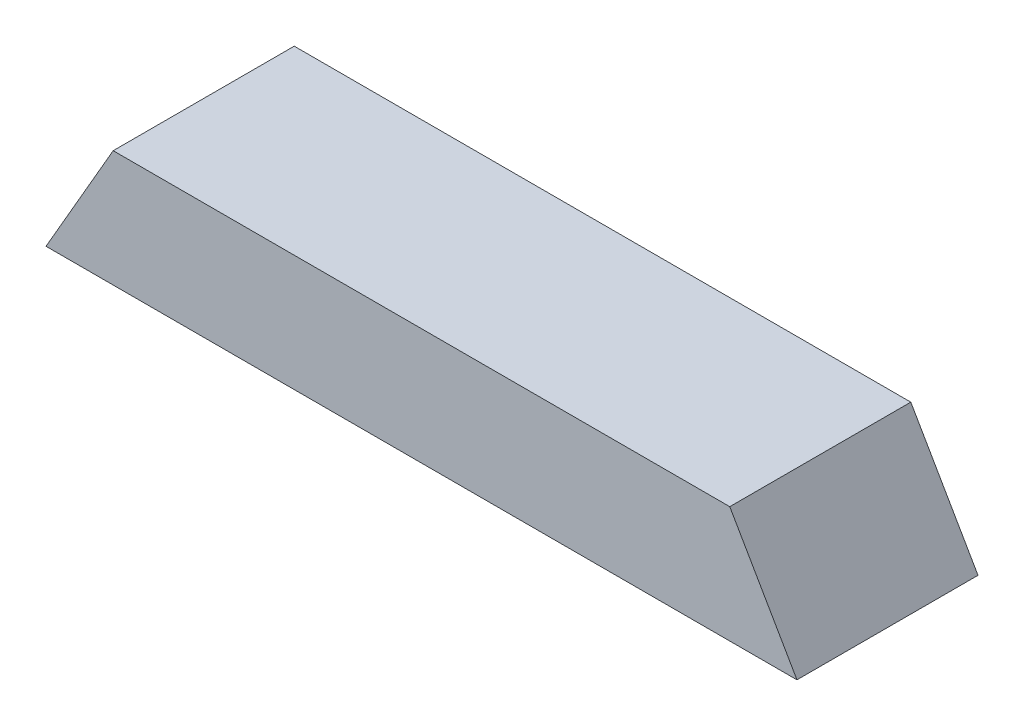
SolidWorks part; units mm, degrees
ref_plane "Front Plane" through (0, 0, 0) normal (0, 0, 1) x (1, 0, 0)
ref_plane "Top Plane" through (0, 0, 0) normal (0, 1, 0) x (1, 0, 0)
ref_plane "Right Plane" through (0, 0, 0) normal (1, 0, 0) x (0, 0, -1)
sketch "Sketch1" plane through (0, 0, 0) normal (0, 1, 0) x (1, 0, 0)
  line L1 (0, 0) -> (26, 0)
  line L2 (0, 0) -> (0, 5.6)
  line L3 (0, 5.6) -> (26, 5.6)
  line L4 (26, 0) -> (26, 5.6)
  dimension "D1" = 26
  dimension "D2" = 5.6
extrude "Boss-Extrude1" add sketch "Sketch1" along normal blind 3.6
chamfer "Chamfer1" distance 6 angle 30 2 edges at (0, 3.6, -2.8) (26, 3.6, -2.8) first distance on face at (0, 1.8, -2.8) first distance on face at (26, 1.8, -2.8)
